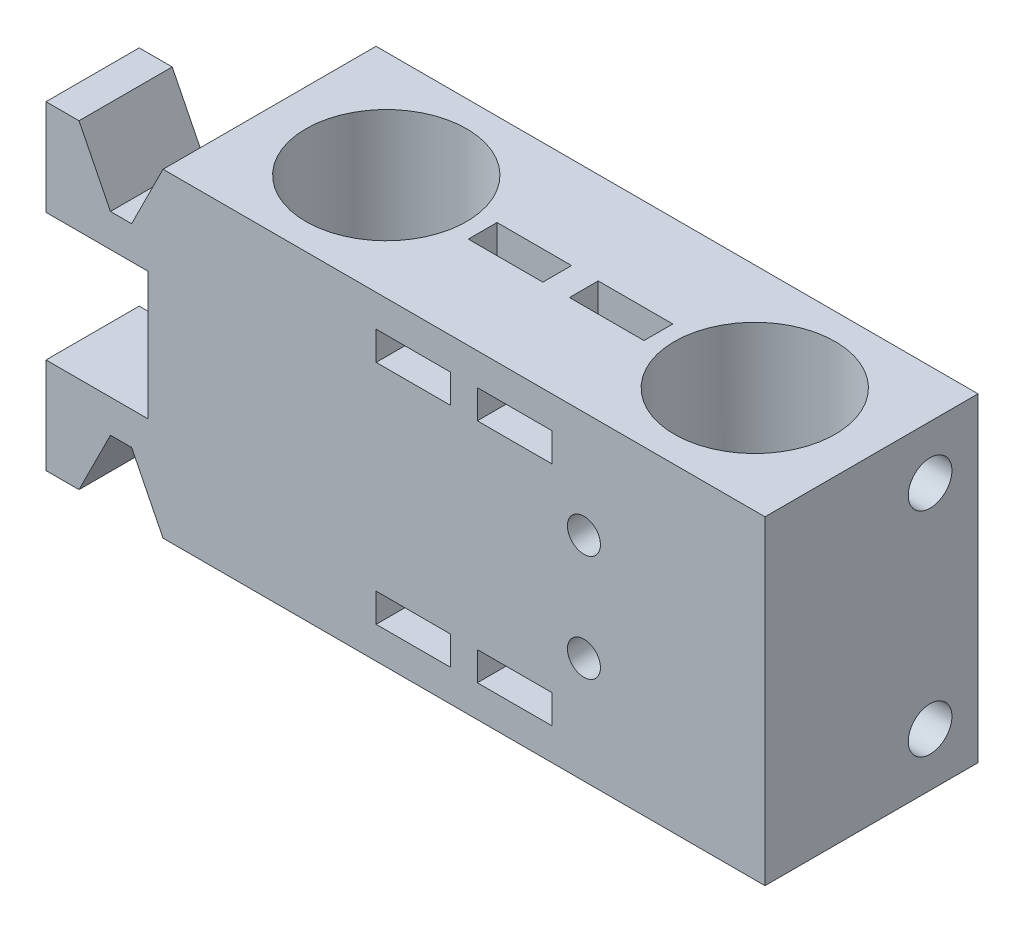
SolidWorks part; units mm, degrees
ref_plane "Front Plane" through (0, 0, 0) normal (0, 0, 1) x (1, 0, 0)
ref_plane "Top Plane" through (0, 0, 0) normal (0, 1, 0) x (1, 0, 0)
ref_plane "Right Plane" through (0, 0, 0) normal (1, 0, 0) x (0, 0, -1)
sketch "BackFace-Sketch1" plane through (0, 0, 0) normal (0, 0, 1) x (1, 0, 0)
  line L0 (0, 0) -> (0, 9)
  line L1 (0, 9) -> (9.6, 9)
  line L2 (9.6, 9) -> (9.6, 21)
  line L3 (9.6, 21) -> (0, 21)
  line L4 (0, 21) -> (0, 30)
  line L5 (0, 30) -> (3.1, 30)
  line L6 (3.1, 30) -> (6.05, 24.096)
  line L7 (6.05, 24.096) -> (8.04, 24.096)
  line L8 (8.04, 24.096) -> (10.99, 30)
  line L9 (10.99, 30) -> (67.51, 30)
  line L10 (67.51, 30) -> (67.51, 0)
  line L12 (10.99, 0) -> (8.04, 5.904)
  line L13 (8.04, 5.904) -> (6.05, 5.904)
  line L14 (6.05, 5.904) -> (3.1, 0)
  line L15 (3.1, 0) -> (0, 0)
  line L23 (67.51, 0) -> (10.99, 0)
  point P13 (4.8, 9)
  point P17 (4.575, 2.952)
  point P18 (7.045, 24.096)
  point P19 (7.045, 5.904)
  dimension "D1" = 3.1
  dimension "D4" = 6.6
  dimension "D5" = 1.99
  dimension "D7" = 30
  dimension "D8" = 9.6
  dimension "D6" = 2.95
  dimension "D12" = 57.91
  dimension "D3" = 56.52
  dimension "D9" = 6.6
extrude "Boss-Extrude1" add sketch "BackFace-Sketch1" along normal blind 20
sketch "EarKnotch-Sketch2" plane through (0, 0, 0) normal (0, 0, -1) x (-1, 0, 0)
  line L0 (-67.51, 30) -> (-10.99, 30) construction
  line L1 (0, 30) -> (-10.99, 30)
  line L2 (0, 30) -> (0, 0)
  line L3 (0, 0) -> (-10.99, 0)
  line L4 (-10.99, 30) -> (-10.99, 0)
  line L8 (0, 30) -> (0, 21) construction
extrude "EarKnotch-Cut-Extrude1" cut sketch "EarKnotch-Sketch2" against normal blind 11.25
sketch "TopHoles-Sketch3" plane through (0, 0, 0) normal (-1, 0, 0) x (0, 0, 1)
  line L0 (20, 30) -> (20, 21) construction
  line L1 (20, 30) -> (11.25, 30) construction
  line L2 (20, 0) -> (11.25, 0) construction
  circle A0 centre (15.5, 25.5) radius 2.05
  circle A1 centre (15.5, 4.5) radius 2.05
  dimension "D4" = 4.1
  dimension "D1" = 4.5
  dimension "D2" = 4.5
  dimension "D3" = 4.5
extrude "TopHoles-Cut-Extrude2" cut sketch "TopHoles-Sketch3" against normal blind 4
sketch "FrontHoles-Sketch1" plane through (0, 0, 0) normal (0, 0, -1) x (-1, 0, 0)
  line L0 (-67.51, 0) -> (-67.51, 30) construction
  line L1 (-67.51, 30) -> (-10.99, 30) construction
  line L3 (-10.99, 0) -> (-67.51, 0) construction
  circle A0 centre (-43.86, 25) radius 2.05
  circle A1 centre (-43.86, 5) radius 2.05
  circle A2 centre (-31.86, 25) radius 2.05
  circle A3 centre (-31.86, 5) radius 2.05
  dimension "D2" = 4.1
  dimension "D1" = 23.65
  dimension "D3" = 12
  dimension "D5" = 5
extrude "FrontHoles-Cut-Extrude1" cut sketch "FrontHoles-Sketch1" against normal blind 7
sketch "RearRibbonHoles-Sketch2" plane through (0, 0, 20) normal (0, 0, 1) x (1, 0, 0)
  line L1 (31, 27) -> (38, 27)
  line L2 (31, 27) -> (31, 24.3)
  line L3 (31, 24.3) -> (38, 24.3)
  line L4 (38, 27) -> (38, 24.3)
  line L5 (40.5, 27) -> (47.5, 27)
  line L6 (40.5, 27) -> (40.5, 24.3)
  line L7 (40.5, 24.3) -> (47.5, 24.3)
  line L8 (47.5, 27) -> (47.5, 24.3)
  line L9 (31, 5.7) -> (38, 5.7)
  line L10 (31, 5.7) -> (31, 3)
  line L11 (31, 3) -> (38, 3)
  line L12 (38, 5.7) -> (38, 3)
  line L13 (40.5, 5.7) -> (47.5, 5.7)
  line L14 (40.5, 5.7) -> (40.5, 3)
  line L15 (40.5, 3) -> (47.5, 3)
  line L16 (47.5, 5.7) -> (47.5, 3)
  line L18 (67.51, 30) -> (10.99, 30) construction
  line L19 (10.99, 0) -> (67.51, 0) construction
  line L22 (67.51, 0) -> (67.51, 30) construction
  dimension "D3" = 2.7
  dimension "D5" = 2.5
  dimension "D2" = 3
  dimension "D7" = 20.01
  dimension "D6" = 20.01
extrude "RearRibbonHoles-Cut-Extrude1" cut sketch "RearRibbonHoles-Sketch2" against normal blind 11.35
sketch "LeftRibbonHoles-Sketch3" plane through (0, 0, 0) normal (0, -1, 0) x (1, 0, 0)
  line L0 (31, 8.65) -> (38, 8.65) construction
  line L1 (31, 11.35) -> (38, 11.35)
  line L2 (31, 11.35) -> (31, 8.65)
  line L3 (31, 8.65) -> (38, 8.65)
  line L4 (38, 11.35) -> (38, 8.65)
  line L5 (40.5, 11.35) -> (47.5, 11.35)
  line L6 (40.5, 11.35) -> (40.5, 8.65)
  line L7 (40.5, 8.65) -> (47.5, 8.65)
  line L8 (47.5, 11.35) -> (47.5, 8.65)
  line L9 (31, 8.65) -> (31, 20) construction
  line L10 (38, 8.65) -> (38, 20) construction
  line L11 (40.5, 8.65) -> (40.5, 20) construction
  line L12 (47.5, 8.65) -> (47.5, 20) construction
  dimension "D1" = 2.7
sketch "RightRibbonHoles-Sketch4" plane through (0, 30, 0) normal (0, 1, 0) x (1, 0, 0)
  line L0 (47.5, -8.65) -> (40.5, -8.65) construction
  line L9 (38, -8.65) -> (31, -8.65) construction
  line L10 (31, -8.65) -> (31, -20) construction
  line L11 (40.5, -8.65) -> (40.5, -20) construction
  line L12 (67.51, -20) -> (10.99, -20) construction
  line L13 (47.5, -8.65) -> (47.5, -20) construction
  line L14 (31, -8.65) -> (38, -8.65)
  line L15 (31, -8.65) -> (31, -11.35)
  line L16 (31, -11.35) -> (38, -11.35)
  line L17 (38, -8.65) -> (38, -11.35)
  line L18 (40.5, -8.65) -> (47.5, -8.65)
  line L19 (40.5, -8.65) -> (40.5, -11.35)
  line L20 (40.5, -11.35) -> (47.5, -11.35)
  line L21 (47.5, -8.65) -> (47.5, -11.35)
  line L22 (38, -8.65) -> (38, -20) construction
  line L23 (38, -8.65) -> (31, -8.65) construction
  line L26 (55.51, -26.7) -> (33.1572, -26.7) construction
  line L27 (50.99, -27.35) -> (33.1572, -27.35) construction
  dimension "D1" = 2.7
  dimension "D2" = 8.65
extrude "RightRibbonHoles-Cut-Extrude2" cut sketch "RightRibbonHoles-Sketch4" against normal blind 5.7
extrude "LeftRibbonHoles-Cut-Extrude2" cut sketch "LeftRibbonHoles-Sketch3" against normal blind 5.7
sketch "BottomClampMountingHolesSketch3" plane through (67.51, 0, 0) normal (1, 0, 0) x (0, 0, -1)
  line L2 (-20, 0) -> (0, 0) construction
  line L3 (-20, 30) -> (0, 30) construction
  line L4 (0, 0) -> (0, 30) construction
  circle A0 centre (-4.5, 25) radius 2.05
  circle A1 centre (-4.5, 5) radius 2.05
  dimension "D1" = 4.1
  dimension "D4" = 4.5
extrude "BottomClampMountHolesCut-Extrude1" cut sketch "BottomClampMountingHolesSketch3" against normal blind 4
sketch "LM8UUHolesSketch1" plane through (0, 30, 0) normal (0, 1, 0) x (1, 0, 0)
  line L0 (67.51, 0) -> (10.99, 0) construction
  line L1 (67.51, -20) -> (67.51, 0) construction
  line L2 (10.99, -11.25) -> (10.99, 0) construction
  circle A0 centre (21.95, -10) radius 7.55
  circle A1 centre (56.55, -10) radius 7.55
  point P9 (67.51, -10)
  dimension "D1" = 15.1
  dimension "D2" = 10
  dimension "D3" = 34.6
  dimension "D4" = 10.96
  dimension "D5" = 10.96
  dimension "D6" = 56.52
extrude "LM8UUCut-Extrude1" cut sketch "LM8UUHolesSketch1" against normal through all
fillet "RibbonHoleFillet2" radius 2.7 1 edges at (34.5, 5.7, 8.65)
fillet "RibbonHoleFillet1" radius 2.7 1 edges at (44, 5.7, 8.65)
fillet "RibbonHoleFillet3" radius 2.7 1 edges at (44, 24.3, 8.65)
fillet "RibbonHoleFillet4" radius 2.7 1 edges at (34.5, 24.3, 8.65)
sketch "ProbeMountingHolesSketch1" plane through (0, 0, 20) normal (0, 0, 1) x (1, 0, 0)
  line L0 (67.51, 30) -> (10.99, 30) construction
  line L1 (10.99, 0) -> (67.51, 0) construction
  line L2 (67.51, 0) -> (67.51, 30) construction
  circle A0 centre (50.51, 20) radius 1.55
  circle A1 centre (50.51, 10) radius 1.55
  dimension "D2" = 10
  dimension "D4" = 3.1
  dimension "D1" = 10
  dimension "D3" = 17
  dimension "D5" = 10
extrude "ProbeMountingHolesCut-Extrude1" cut sketch "ProbeMountingHolesSketch1" against normal blind 3.1
sketch "LM8UUFasteningHoleSketch1" plane through (0, 0, 0) normal (0, 0, -1) x (-1, 0, 0)
  line L0 (-56.55, 0) -> (-56.55, 30) construction
  line L1 (-21.95, 0) -> (-21.95, 30) construction
  line L2 (-67.51, 30) -> (-10.99, 30) construction
  circle A0 centre (-30.55, 15) radius 2.1
  circle A1 centre (-47.95, 15) radius 2.1
  dimension "D4" = 4.2
  dimension "D1" = 8.6
  dimension "D3" = 15
extrude "LM8UUFasteningHoleCut-Extrude1" cut sketch "LM8UUFasteningHoleSketch1" against normal blind 14
equation "\"LinearGBWidth\"= 27mm'Spec"
equation "\"CarrierRibbonHoleWidth\"= 7mm"
equation "\"CarrierRibbonHoleHeight\"= 2.7mm"
equation "\"CarrierRibbonHoleDistance\"= 2.5mm'Equals 2.5. Must equal distance created by GABRiserBossOffset"
equation "\"CarrierRibbonHoleOffsetFromSide\"= 3.0mm"
equation "\"CarrierDepth\"= 20mm'From the100"
equation "\"D1@Boss-Extrude1\"=\"CarrierDepth\""
equation "\"D3@RearRibbonHoles-Sketch2\" = \"CarrierRibbonHoleHeight\""
equation "\"D4@RearRibbonHoles-Sketch2\" = \"CarrierRibbonHoleWidth\""
equation "\"D5@RearRibbonHoles-Sketch2\" = \"CarrierRibbonHoleDistance\""
equation "\"D1@RightRibbonHoles-Cut-Extrude2\" = \"CarrierRibbonHoleOffsetFromSide\" + \"CarrierRibbonHoleHeight\""
equation "\"D1@LeftRibbonHoles-Cut-Extrude2\" = \"CarrierRibbonHoleOffsetFromSide\" + \"CarrierRibbonHoleHeight\""
equation "\"D1@RightRibbonHoles-Sketch4\"=\"CarrierRibbonHoleHeight\""
equation "\"D1@RearRibbonHoles-Cut-Extrude1\"=\"CarrierDepth\" / 2 + \"CarrierRibbonHoleHeight\"/2"
equation "\"D1@LeftRibbonHoles-Sketch3\"=\"CarrierRibbonHoleHeight\""
equation "\"AngledCarrierBodyLength\"= \"CarrierBodyLength\" - 1.39mm'From the 100 1.39 accounts for the little slant"
equation "\"M3HeatInsertHoleDiameter\"= 4mm + .1mm'Add .1mm for printing"
equation "\"D1@BottomClampMountingHolesSketch3\"=\"M3HeatInsertHoleDiameter\""
equation "\"M3HeatInsertHoleDepth\"= 4mm"
equation "\"D1@BottomClampMountHolesCut-Extrude1\"=\"M3HeatInsertHoleDepth\""
equation "\"D1@RibbonHoleFillet1\" = \"CarrierRibbonHoleHeight\""
equation "\"D1@RibbonHoleFillet2\"=\"CarrierRibbonHoleHeight\""
equation "\"D1@RibbonHoleFillet3\"=\"CarrierRibbonHoleHeight\""
equation "\"D1@RibbonHoleFillet4\"=\"CarrierRibbonHoleHeight\""
equation "\"D4@TopHoles-Sketch3\"=\"M3HeatInsertHoleDiameter\""
equation "\"D2@FrontHoles-Sketch1\"=\"M3HeatInsertHoleDiameter\""
equation "\"D3@BackFace-Sketch1\"= \"AngledCarrierBodyLength\""
equation "\"D1@RearRibbonHoles-Sketch2\"=\"CarrierRibbonHoleOffsetFromSide\""
equation "\"D2@RearRibbonHoles-Sketch2\"=\"CarrierRibbonHoleOffsetFromSide\""
equation "\"D2@LM8UUHolesSketch1\"=\"CarrierDepth\" / 2 "
equation "\"GABDistanceBetweenXAxisRods\"= 34.6mm'From the100"
equation "\"D3@LM8UUHolesSketch1\"=\"GABDistanceBetweenXAxisRods\""
equation "\"LM8UUDiameter\"= 15mm"
equation "\"D1@LM8UUHolesSketch1\"=\"LM8UUDiameter\" + .1mm"
equation "\"CarrierBodyLength\"= 57.91mm"
equation "\"D4@LM8UUHolesSketch1\" = ( \"AngledCarrierBodyLength\" - \"GABDistanceBetweenXAxisRods\" ) / 2"
equation "\"D6@RearRibbonHoles-Sketch2\"=(\"AngledCarrierBodyLength\" - \"CarrierRibbonHoleWidth\" * 2 - \"CarrierRibbonHoleDistance\")/2"
equation "\"CarrierWidth\"= 30mm"
equation "\"D7@BackFace-Sketch1\"=\"CarrierWidth\""
equation "\"D2@ProbeMountingHolesSketch1\" =  ( \"CarrierWidth\" - \"ProbeDistanceBetweenMountingHoles\" )  / 2"
equation "\"M2HeatInsertHoleDiameter\"= 3mm + .1mm'Add .1mm for printing"
equation "\"M2HeatInsertHoleDepth\"= 3.1mm'Spec"
equation "\"D4@ProbeMountingHolesSketch1\" = \"M2HeatInsertHoleDiameter\""
equation "\"D1@ProbeMountingHolesCut-Extrude1\" = \"M2HeatInsertHoleDepth\""
equation "\"ProbeDistanceBetweenMountingHoles\" = 10mm"
equation "\"D1@ProbeMountingHolesSketch1\" = \"ProbeDistanceBetweenMountingHoles\""
equation "\"LM8UUFasteningHoleDiameter\"= 4.2mm'10/24 set screw hole diameter"
equation "\"D1@LM8UUFasteningHoleSketch1\" = \"LM8UUDiameter\" / 2 + \"LM8UUFasteningHoleDiameter\" / 2 - 1mm"
equation "\"D2@LM8UUFasteningHoleSketch1\" = \"LM8UUDiameter\" / 2 + \"LM8UUFasteningHoleDiameter\" / 2 - 1mm"
equation "\"D3@LM8UUFasteningHoleSketch1\" = \"CarrierWidth\" / 2"
equation "\"D1@LM8UUFasteningHoleCut-Extrude1\"= \"CarrierDepth\" / 2 + 4mm'Odd that up to next does not work properly"
